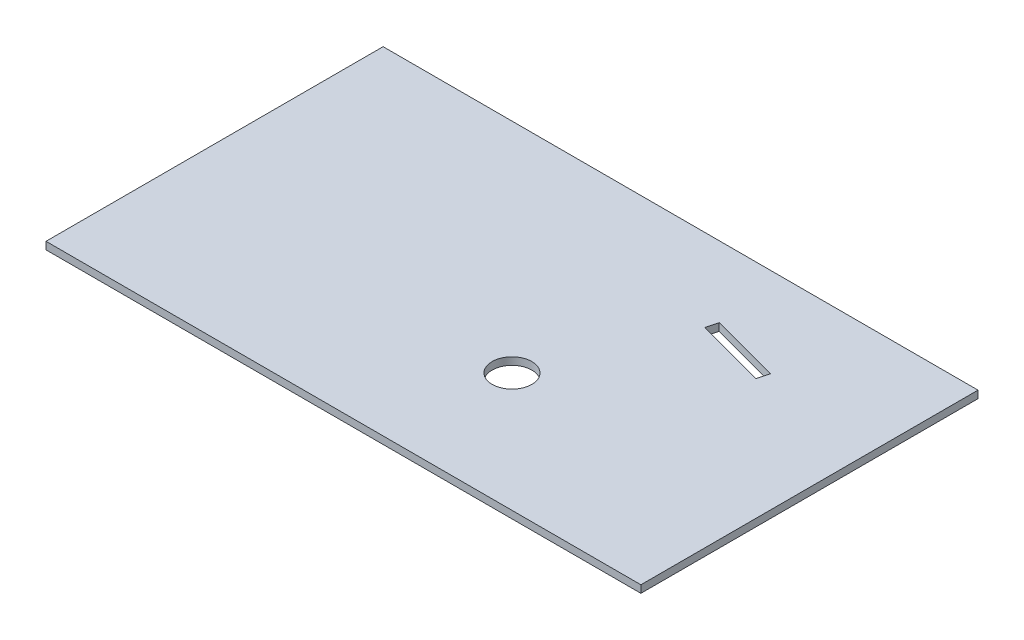
SolidWorks part; units mm, degrees
material "Particle Board"
ref_plane "Front Plane" through (0, 0, 0) normal (0, 0, 1) x (1, 0, 0)
ref_plane "Top Plane" through (0, 0, 0) normal (0, 1, 0) x (1, 0, 0)
ref_plane "Right Plane" through (0, 0, 0) normal (1, 0, 0) x (0, 0, -1)
sketch "Sketch3" plane through (0, 0, 0) normal (0, 1, 0) x (1, 0, 0)
  line L1 (0, 0) -> (-839.8654, 0) construction
  line L2 (0, 0) -> (-451.1992, 260.5) construction
  line L5 (-524, 0) -> (-525.5875, 0)
  line L6 (277.6777, 444.3772) -> (277.6777, 446.248)
  circle A0 centre (0, 0) radius 254 construction
  arc A3 (277.6777, 444.3772) -> (-524, 0) centre (0, 0) ccw
  arc A4 (277.6777, 446.248) -> (-525.5875, 0) centre (0, 0) ccw
  arc A5 (278.5189, 445.7235) -> (-525.5875, 0) centre (0, 0) ccw construction
  dimension "D1" = 524
  dimension "D2" = 1.5875
  dimension "D4" = 122
  dimension "D5" = 508
  dimension "D3" = 30
extrude "Boss-Extrude1" add sketch "Sketch3" along normal blind 50.8
sketch "Sketch4" plane through (0, 50.8, 0) normal (0, 1, 0) x (1, 0, 0)
  line L5 (-889, 558.8) -> (635, 558.8)
  line L6 (-889, 558.8) -> (-889, -304.8)
  line L7 (-889, -304.8) -> (635, -304.8)
  line L8 (635, 558.8) -> (635, -304.8)
  dimension "D1" = 304.8
  dimension "D2" = 1524
  dimension "D3" = 863.6
  dimension "D4" = 635
extrude "Boss-Extrude2" add sketch "Sketch4" along normal blind 19.05
hole_wizard "Ø20.0mm Dowel Hole1" positions "Sketch6" profile "Sketch7" hole size "Ø20.0" standard "ANSI Metric" end condition through all
sketch "Sketch6" plane through (0, 50.8, 0) normal (0, -1, 0) x (-1, 0, 0)
  point P0 (0, 0)
sketch "Sketch7" plane through (0, 50.8, 0) normal (1, 0, 0) x (0, 0, -1)
  line L0 (0, 0) -> (0, 19.05)
  line L1 (0, 19.05) -> (50.8, 19.05)
  line L2 (50.8, 19.05) -> (50.8, 0)
  line L5 (50.8, 0) -> (0, 0)
  line L11 (0, -6.35) -> (0, 107.95) construction
  dimension "Thru Hole Dia." = 101.6
  dimension "Thru Hole Depth" = 19.05
ref_plane "Plane1" through (0, 0, 298.45) normal (0, 0, 1) x (1, 0, 0)
sketch "Sketch8" plane through (0, 0, 0) normal (0, 0, 1) x (1, 0, 0)
  line L0 (-524, 50.8) -> (-524, 0) construction
  line L1 (-525.5875, 50.8) -> (-524, 50.8)
  line L2 (-525.5875, 50.8) -> (-525.5875, 0)
  line L3 (-525.5875, 0) -> (-524, 0)
  line L4 (-524, 50.8) -> (-524, 0)
  line L5 (-525.5875, 50.8) -> (-525.5875, 0) construction
  line L6 (-525.5875, 0) -> (-524, 0) construction
  line L7 (-525.5875, 50.8) -> (-524, 50.8) construction
extrude "Boss-Extrude3" add sketch "Sketch8" along normal blind 204
sketch "Sketch9" plane through (0, 50.8, 0) normal (0, -1, 0) x (-1, 0, 0)
  line L0 (-154.0683, 376.8593) -> (-332.7646, 328.9778)
  line L1 (-332.7646, 328.9778) -> (-325, 300)
  line L2 (-325, 300) -> (-146.3037, 347.8815)
  line L3 (-146.3037, 347.8815) -> (-154.0683, 376.8593)
  line L6 (0, 0) -> (-635, 0) construction
  line L7 (-635, -304.8) -> (-635, 558.8) construction
  dimension "D1" = 185
  dimension "D2" = 30
  dimension "D3" = 15
  dimension "D4" = 325
  dimension "D5" = 300
extrude "Cut-Extrude1" cut sketch "Sketch9" against normal through all
sketch "Sketch10" plane through (0, 69.85, 0) normal (0, -1, 0) x (-1, 0, 0)
  line L0 (0, 0) -> (-545.6, 0) construction
  line L1 (0, 0) -> (277.6777, 444.3772) construction
  line L2 (0, 0) -> (195.5256, 509.3615) construction
  line L3 (0, 0) -> (94.7424, 537.3111) construction
  circle A0 centre (0, 0) radius 545.6 construction
  dimension "D1" = 11
  dimension "D2" = 11
ref_axis "WHEEL CENTER" through (-565.7508, 50.8, 0) along (1, 0, 0)
ref_plane "BASE CENTER" through (-127, 0, 0) normal (1, 0, 0) x (0, 0, -1)
